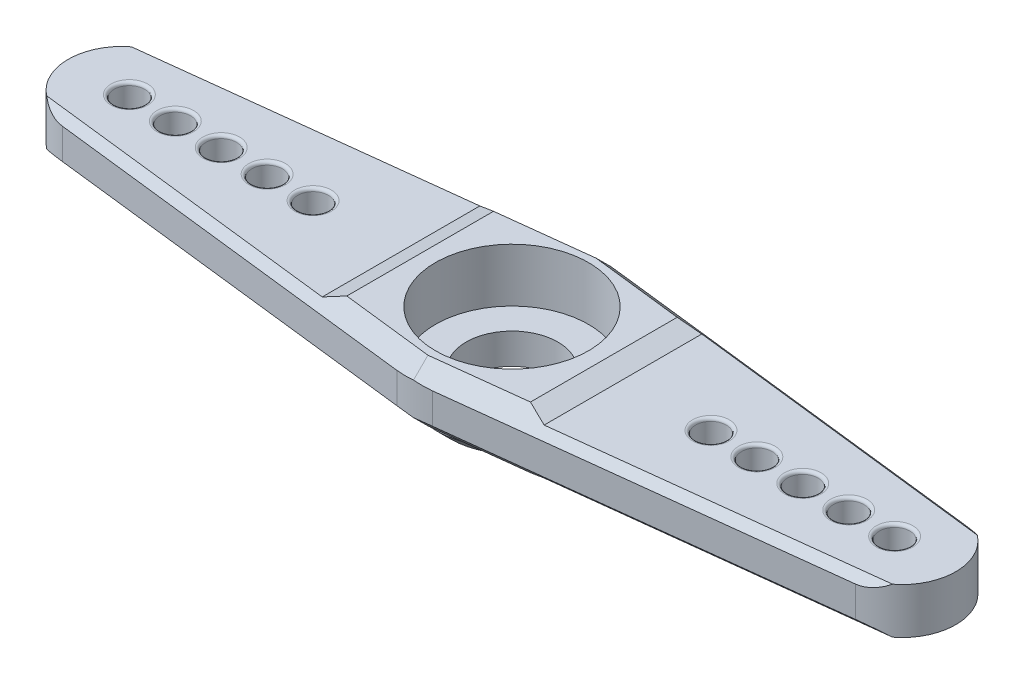
SolidWorks part; units mm, degrees
ref_plane "Спереди" through (0, 0, 0) normal (0, 0, 1) x (1, 0, 0)
ref_plane "Сверху" through (0, 0, 0) normal (0, 1, 0) x (1, 0, 0)
ref_plane "Справа" through (0, 0, 0) normal (1, 0, 0) x (0, 0, -1)
other "Configuration Table"
sketch "Эскиз2" plane through (0, 0, 0) normal (0, 1, 0) x (1, 0, 0)
  line L0 (0, -6.5) -> (0, 6.5)
  line L1 (0, 0) -> (0, 35.4765) construction
  line L2 (0, 0) -> (37.9876, 0) construction
  line L3 (-29, 0) -> (-29, 7.5928) construction
  line L4 (29, 0) -> (29, 5.1836) construction
  line L5 (0, -6.5) -> (-25.9057, -3.4764)
  line L6 (0, 6.5) -> (-25.9057, 3.4764)
  line L7 (0, 6.5) -> (25.9057, 3.4764)
  line L8 (0, -6.5) -> (25.9057, -3.4764)
  line L9 (8.5, -5.5079) -> (8.5, 5.5079)
  line L10 (-8.5, 5.5079) -> (-8.5, -5.5079)
  circle A0 centre (0, 0) radius 3.5
  circle A1 centre (0, 0) radius 3
  arc A2 (25.9057, -3.4764) -> (25.9057, 3.4764) centre (25.5, 0) ccw
  arc A3 (-25.9057, 3.4764) -> (-25.9057, -3.4764) centre (-25.5, 0) ccw
  circle A4 centre (0, 0) radius 5
  dimension "D1" = 7
  dimension "D2" = 6
  dimension "D5" = 7
  dimension "D6" = 10
  dimension "D3" = 13
  dimension "D4" = 58
  dimension "D7" = 17
extrude "Бобышка-Вытянуть1" add sketch "Эскиз2" along normal blind 3 contours L6 A3 L5 L10 | A4 L0 L6 L10 L5 | A4 L0 L8 L9 L7 | L8 A2 L7 L9 region at (-5.3905, 0, 0) region at (5.3905, 0, 0) region at (-17.5592, 0, 0) region at (17.5592, 0, 0)
extrude "Бобышка-Вытянуть2" add sketch "Эскиз2<3>" against normal blind 2 separate body contours L0 A4 A0 | L0 A4 A0 | A1 L0 A0 | A1 L0 A0 region at (-4.8882, 0, 0) region at (0.1118, 0, 4.25) region at (-3.4217, 0, 0) region at (0.0783, 0, 3.25)
sketch "Эскиз2<3>" plane through (0, 0, 0) normal (0, 1, 0) x (1, 0, 0) same geometry as "Эскиз2"
extrude "Бобышка-Вытянуть3" add sketch "Эскиз2<5>" against normal blind 0.5 contours A4 L0 L6 L10 L5 | A4 L0 L8 L9 L7 region at (-5.3905, 0, 0) region at (5.3905, 0, 0)
sketch "Эскиз2<5>" plane through (0, 0, 0) normal (0, 1, 0) x (1, 0, 0) same geometry as "Эскиз2"
extrude "Бобышка-Вытянуть4" add sketch "Эскиз2<6>" along normal blind 0.5 from surface contours A4 L0 L8 L9 L7 | A4 L0 L6 L10 L5 region at (-5.3905, 0, 0) region at (5.3905, 0, 0) starting at face at (0, 3, 0)
sketch "Эскиз2<6>" plane through (0, 0, 0) normal (0, 1, 0) x (1, 0, 0) same geometry as "Эскиз2"
chamfer "Фаска2" distance 1 angle 45 1 edges at (0, -2, 5)
chamfer "Фаска3" distance 2.5 distance2 1 4 edges at (-8.5, 3.5, 0) (8.5, 3.5, 0) (8.5, -0.5, 0) (-8.5, -0.5, 0) first distance on face at (0, 3.5, 0) first distance on face at (0, -0.5, 0)
chamfer "Фаска4" distance 1 angle 45 8 edges at (-3, -0.5, -6.1499) (3, -0.5, -6.1499) (-3, -0.5, 6.1499) (3, -0.5, 6.1499) (3, 3.5, -6.1499) (-3, 3.5, -6.1499) (-3, 3.5, 6.1499) (3, 3.5, 6.1499)
fillet "Скругление1" radius 10 2 edges at (0, 1.5, -6.5) (0, 1.5, 6.5)
sketch "Эскиз3" plane through (0, 3, 0) normal (0, 1, 0) x (1, 0, 0)
  line L0 (0, 0) -> (34.464, 0) construction
  line L1 (0, 0) -> (0, 15.803) construction
  circle A0 centre (-13, 0) radius 1
  circle A1 centre (-16, 0) radius 1
  circle A2 centre (-19, 0) radius 1
  circle A3 centre (-22, 0) radius 1
  circle A4 centre (-25, 0) radius 1
  circle A5 centre (25, 0) radius 1
  circle A6 centre (22, 0) radius 1
  circle A7 centre (19, 0) radius 1
  circle A8 centre (16, 0) radius 1
  circle A9 centre (13, 0) radius 1
  dimension "D1" = 2
  dimension "D2" = 13
  dimension "D3" = 5
extrude "Вырез-Вытянуть1" cut sketch "Эскиз3" against normal through all
fillet "Скругление2" radius 0.2 20 edges at (13, 0, 1) (13, 3, -1) (25, 0, 1) (25, 3, -1) (16, 0, 1) (16, 3, -1) (19, 0, 1) (19, 3, -1) (22, 0, 1) (22, 3, -1) (-13, 0, 1) (-13, 3, 1) (-16, 0, 1) (-16, 3, 1) (-19, 0, 1) (-19, 3, 1) (-22, 0, 1) (-22, 3, 1) (-25, 0, 1) (-25, 3, 1)
